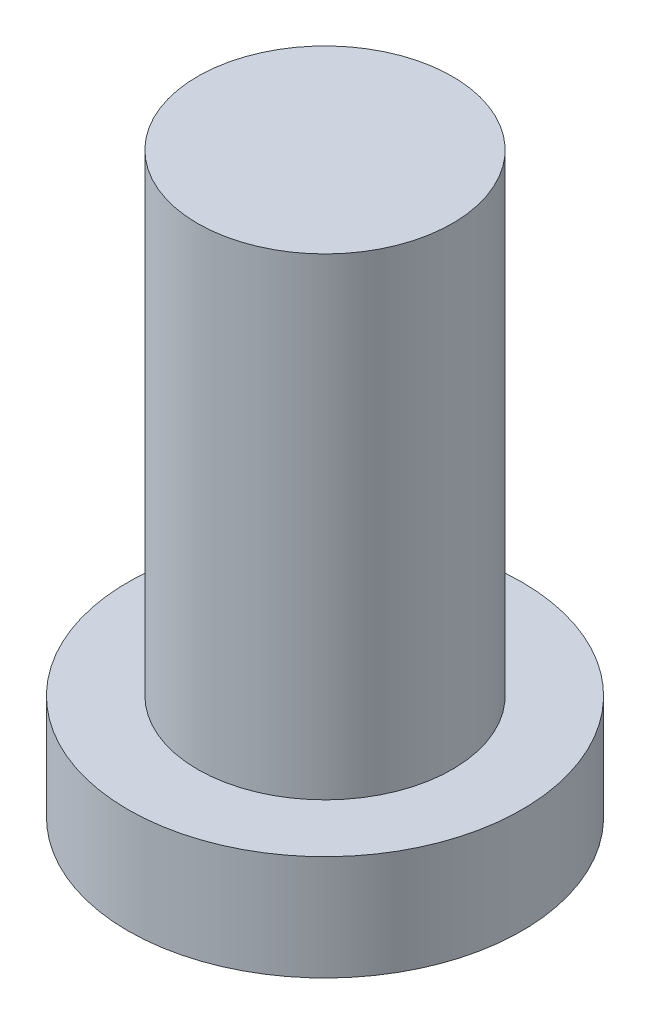
SolidWorks part; units mm, degrees
ref_plane "Front Plane" through (0, 0, 0) normal (0, 0, 1) x (1, 0, 0)
ref_plane "Top Plane" through (0, 0, 0) normal (0, 1, 0) x (1, 0, 0)
ref_plane "Right Plane" through (0, 0, 0) normal (1, 0, 0) x (0, 0, -1)
sketch "Sketch1" plane through (0, 0, 0) normal (0, 1, 0) x (1, 0, 0)
  circle A0 centre (0, 0) radius 7.5
  dimension "D1" = 15
extrude "Boss-Extrude1" add sketch "Sketch1" along normal blind 4
sketch "Sketch2" plane through (0, 4, 0) normal (0, 1, 0) x (1, 0, 0)
  circle A0 centre (0, 0) radius 4.85
  dimension "D1" = 9.7
extrude "Boss-Extrude5" add sketch "Sketch2" along normal blind 18
